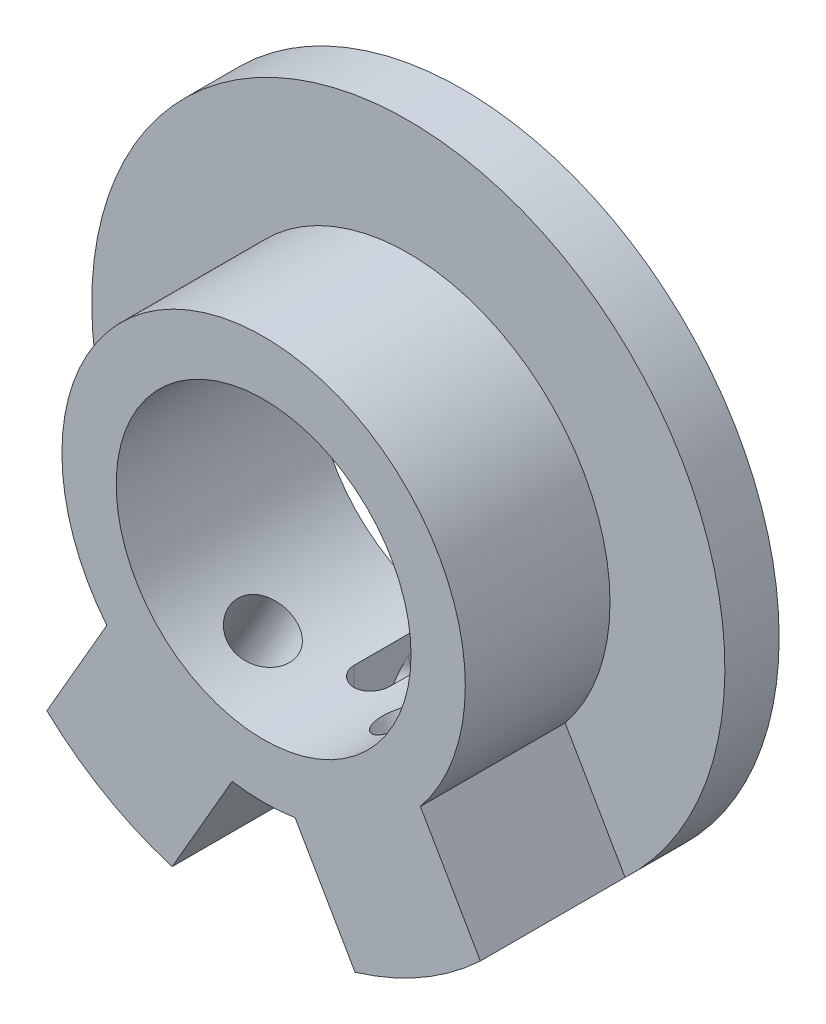
SolidWorks part; units mm, degrees
ref_plane "Top Plane" through (0, 0, 0) normal (0, 0, 1) x (1, 0, 0)
ref_plane "Right Plane" through (0, 0, 0) normal (0, 1, 0) x (1, 0, 0)
ref_plane "Front Plane" through (0, 0, 0) normal (1, 0, 0) x (0, 0, -1)
sketch "Sketch1" plane through (0, 0, 0) normal (0, 0, 1) x (1, 0, 0)
  circle A0 centre (0, 0) radius 8.15
  circle A1 centre (0, 0) radius 17.5
  dimension "D1" = 16.3
  dimension "D2" = 35
extrude "Boss-Extrude1" add sketch "Sketch1" along normal blind 3
sketch "Sketch2" plane through (0, 0, 3) normal (0, 0, 1) x (1, 0, 0)
  circle A0 centre (0, 0) radius 8.15
  circle A1 centre (0, 0) radius 11.15
  circle A2 centre (0, 0) radius 8.15 construction
  point P5 (0, 0)
  dimension "D1" = 3
extrude "Boss-Extrude2" add sketch "Sketch2" along normal blind 8
ref_plane "Plane1" through (-5.575, -9.6562, 0) normal (-0.5, -0.866, 0) x (0, 0, -1)
sketch "Sketch4" plane through (-5.575, -9.6562, 0) normal (-0.5, -0.866, 0) x (0, 0, -1)
  line L0 (0, 0) -> (-3, 0) construction
  line L1 (-3, 0) -> (-11, 0) construction
  line L2 (-11, -4) -> (-11, 4)
  line L3 (-3, 11.15) -> (-3, -11.15) construction
  line L4 (-11, 11.15) -> (-11, -11.15) construction
  line L5 (-11, -4) -> (-3, -4)
  line L6 (-3, -4) -> (-3, 4)
  line L7 (-3, 4) -> (-11, 4)
  dimension "D1" = 8
extrude "Boss-Extrude5" add sketch "Sketch4" along normal up to surface and the other way up to surface up to face at (17.5, 0, 3) other way up to face at (8.15, 0, 0)
sketch "Sketch3" plane through (-5.575, -9.6562, 0) normal (-0.5, -0.866, 0) x (0, 0, -1)
  line L0 (-3, 0) -> (-11, 0) construction
  line L1 (-11, 11.15) -> (-11, -11.15) construction
  line L2 (-3, 0) -> (0, 0) construction
  line L3 (-3, 11.15) -> (-3, -11.15) construction
  circle A0 centre (-7, 0) radius 1.65
  point P5 (0, 0)
  dimension "D1" = 3.3
extrude "Cut-Extrude1" cut sketch "Sketch3" against normal up to surface and the other way through all up to face at (8.15, 0, 11)
mirror "Mirror1" about plane through (0, 0, 0) normal (1, 0, 0) of "Cut-Extrude1", "Boss-Extrude5"
sketch "Sketch5" plane through (0, 0, 3) normal (0, 0, 1) x (1, 0, 0)
  line L0 (-1, -9.0884) -> (-1, -8.0884)
  line L1 (-1, -8.0884) -> (1, -8.0884)
  line L2 (1, -8.0884) -> (1, -9.0884)
  arc A0 (-1, -9.0884) -> (1, -9.0884) centre (0, -9.0884) ccw
  arc A1 (1, -9.0884) -> (-1, -9.0884) centre (0, -9.0884) ccw construction
  circle A2 centre (0, 0) radius 8.15 construction
  point P1 (0, 0)
  point P4 (0, 0)
  point P9 (0, 0)
  dimension "D1" = 2
extrude "Cut-Extrude2" cut sketch "Sketch5" against normal through all and the other way blind 3
sketch "Sketch6" plane through (0, 0, 3) normal (0, 0, 1) x (1, 0, 0)
  line L1 (-1, -8.0884) -> (1, -8.0884)
  line L2 (-1, -8.0884) -> (-1, -17.4714)
  line L3 (-1, -17.4714) -> (1, -17.4714)
  line L4 (1, -8.0884) -> (1, -17.4714)
  arc A0 (-5.0543, -16.7542) -> (5.0543, -16.7542) centre (0, 0) ccw construction
  point P5 (0.75, -8.1154)
  point P7 (0.75, -17.4839)
extrude "Cut-Extrude3" cut sketch "Sketch6" along normal up to surface (3 mm away) up to face at (0, -8.8538, 6)
fillet "Fillet2" radius 1 3 edges at (1, -9.5967, 6) (-1, -9.5967, 6) (0, -10.0884, 3)
